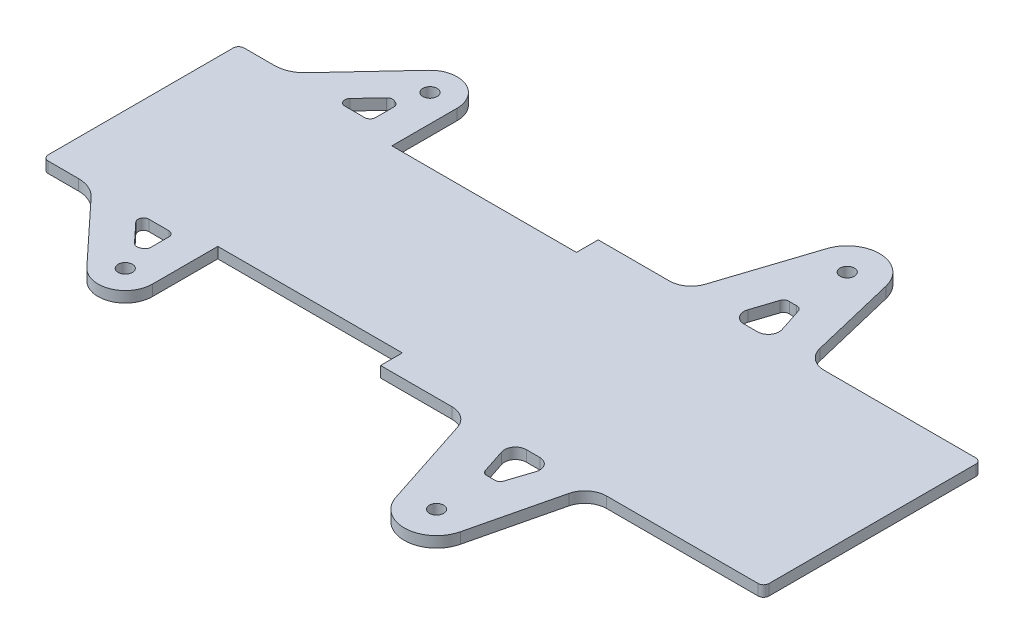
SolidWorks part; units mm, degrees
ref_plane "Front Plane" through (0, 0, 0) normal (0, 0, 1) x (1, 0, 0)
ref_plane "Top Plane" through (0, 0, 0) normal (0, 1, 0) x (1, 0, 0)
ref_plane "Right Plane" through (0, 0, 0) normal (1, 0, 0) x (0, 0, -1)
sketch "Sketch1" plane through (0, 0, 0) normal (0, 1, 0) x (1, 0, 0)
  line L0 (-64.5699, 0) -> (82.804, 0) construction
  line L1 (26.924, -25.4) -> (-26.924, -25.4)
  line L2 (71.424, -59.917) -> (71.424, 59.917) construction
  line L3 (26.924, 25.4) -> (-26.924, 25.4)
  line L4 (26.924, 25.4) -> (26.924, 31.75)
  line L5 (26.924, -25.4) -> (-26.924, 25.4) construction
  line L6 (26.924, 25.4) -> (-26.924, -25.4) construction
  line L7 (-26.924, 25.4) -> (-26.924, 28.575)
  line L8 (-47.4926, -28.575) -> (-39.004, -37.6792)
  line L9 (-26.924, 28.575) -> (-26.924, 44.45)
  line L10 (-60.5155, -28.575) -> (-40.667, -49.8629)
  line L11 (-26.924, -44.45) -> (-26.924, -25.4)
  line L12 (-46.228, -28.575) -> (-26.924, 28.575) construction
  line L13 (-46.228, 28.575) -> (-26.924, -28.575) construction
  line L14 (52.324, -31.75) -> (26.924, -31.75)
  line L15 (138.684, -31.75) -> (138.684, 31.75)
  line L16 (138.684, 31.75) -> (87.884, 31.75)
  line L17 (26.924, -31.75) -> (26.924, -25.4)
  line L18 (138.684, -31.75) -> (26.924, 31.75) construction
  line L19 (138.684, 31.75) -> (26.924, -31.75) construction
  line L20 (52.324, 31.75) -> (62.6076, 63.2401)
  line L21 (52.324, -31.75) -> (62.6076, -63.2401)
  line L22 (52.324, 31.75) -> (26.924, 31.75)
  line L23 (87.884, 31.75) -> (80.5851, 62.1188)
  line L24 (138.684, -31.75) -> (87.884, -31.75)
  line L25 (87.884, -31.75) -> (80.5851, -62.1188)
  line L26 (77.774, 31.75) -> (65.074, 31.75)
  line L27 (65.074, 31.75) -> (69.142, 44.2069)
  line L28 (77.774, 31.75) -> (73.706, 44.2069)
  line L29 (77.774, -31.75) -> (73.706, -44.2069)
  line L30 (65.074, -31.75) -> (69.142, -44.2069)
  line L31 (77.774, -31.75) -> (65.074, -31.75)
  line L32 (-34.8615, -44.45) -> (-34.8615, 44.45) construction
  line L33 (-60.5155, 28.575) -> (-40.667, 49.8629)
  line L34 (-74.803, -28.575) -> (-60.5155, -28.575)
  line L35 (-74.803, -28.575) -> (-74.803, 28.575)
  line L36 (-74.803, 28.575) -> (-60.5155, 28.575)
  line L38 (-74.803, -28.575) -> (-46.228, 28.575) construction
  line L39 (-74.803, 28.575) -> (-46.228, -28.575) construction
  line L40 (-36.449, -28.575) -> (-36.449, -36.6729)
  line L41 (-47.4926, -28.575) -> (-36.449, -28.575)
  line L42 (-47.4926, 28.575) -> (-36.449, 28.575)
  line L43 (-36.449, 28.575) -> (-36.449, 36.6729)
  line L44 (-47.4926, 28.575) -> (-39.004, 37.6792)
  circle A0 centre (71.424, 59.917) radius 2.0828
  arc A1 (80.5851, 62.1188) -> (62.6076, 63.2401) centre (71.424, 59.917) ccw
  arc A2 (80.5851, -62.1188) -> (62.6076, -63.2401) centre (71.424, -59.917) cw
  arc A3 (69.142, -44.2069) -> (73.706, -44.2069) centre (71.424, -59.917) cw
  arc A4 (69.142, 44.2069) -> (73.706, 44.2069) centre (71.424, 59.917) ccw
  circle A5 centre (-34.8615, 44.45) radius 2.0828
  circle A6 centre (71.424, -59.917) radius 2.0828
  arc A7 (-26.924, 44.45) -> (-40.667, 49.8629) centre (-34.8615, 44.45) ccw
  arc A8 (-40.667, -49.8629) -> (-26.924, -44.45) centre (-34.8615, -44.45) ccw
  circle A9 centre (-34.8615, -44.45) radius 2.0828
  arc A10 (-36.449, 36.6729) -> (-39.004, 37.6792) centre (-34.8615, 44.45) cw
  arc A11 (-36.449, -36.6729) -> (-39.004, -37.6792) centre (-34.8615, -44.45) ccw
  point P0 (0, 0)
  point P8 (-36.576, 0)
  point P20 (71.424, 0)
  point P31 (138.684, 0)
  point P37 (71.424, 31.75)
  point P42 (71.424, -31.75)
  point P43 (-60.5155, 0)
  point P46 (-34.8615, 0)
  dimension "D9" = 4.1656
  dimension "D10" = 50.8
  dimension "D13" = 7.9375
  dimension "D15" = 15.875
  dimension "D16" = 28.575
  dimension "D18" = 4.1656
  dimension "D19" = 15.875
  dimension "D1" = 53.848
  dimension "D2" = 50.8
  dimension "D3" = 57.15
  dimension "D4" = 19.304
  dimension "D5" = 111.76
  dimension "D6" = 63.5
  dimension "D7" = 119.834
  dimension "D8" = 44.5
  dimension "D11" = 25.4
  dimension "D12" = 63.5
  dimension "D14" = 12.7
  dimension "D17" = 88.9
  dimension "D21" = 9.525
extrude "Boss-Extrude1" add sketch "Sketch1" along normal blind 3.175
fillet "Fillet1" radius 1.5875 4 edges at (73.706, 1.5875, -44.2069) (69.142, 1.5875, -44.2069) (73.706, 1.5875, 44.2069) (69.142, 1.5875, 44.2069)
fillet "Fillet2" radius 3.175 4 edges at (77.774, 1.5875, 31.75) (65.074, 1.5875, 31.75) (77.774, 1.5875, -31.75) (65.074, 1.5875, -31.75)
fillet "Fillet3" radius 1.5875 2 edges at (138.684, 1.5875, -31.75) (138.684, 1.5875, 31.75)
fillet "Fillet4" radius 6.35 4 edges at (52.324, 1.5875, -31.75) (87.884, 1.5875, -31.75) (87.884, 1.5875, 31.75) (52.324, 1.5875, 31.75)
fillet "Fillet5" radius 8.89 2 edges at (-60.5155, 1.5875, -28.575) (-60.5155, 1.5875, 28.575)
fillet "Fillet6" radius 1.5875 2 edges at (-74.803, 1.5875, 28.575) (-74.803, 1.5875, -28.575)
fillet "Fillet7" radius 1.5875 2 edges at (-36.449, 1.5875, -28.575) (-36.449, 1.5875, 28.575)
fillet "Fillet8" radius 1.5875 6 edges at (-36.449, 1.5875, 36.6729) (-39.004, 1.5875, 37.6792) (-47.4926, 1.5875, 28.575) (-36.449, 1.5875, -36.6729) (-39.004, 1.5875, -37.6792) (-47.4926, 1.5875, -28.575)
